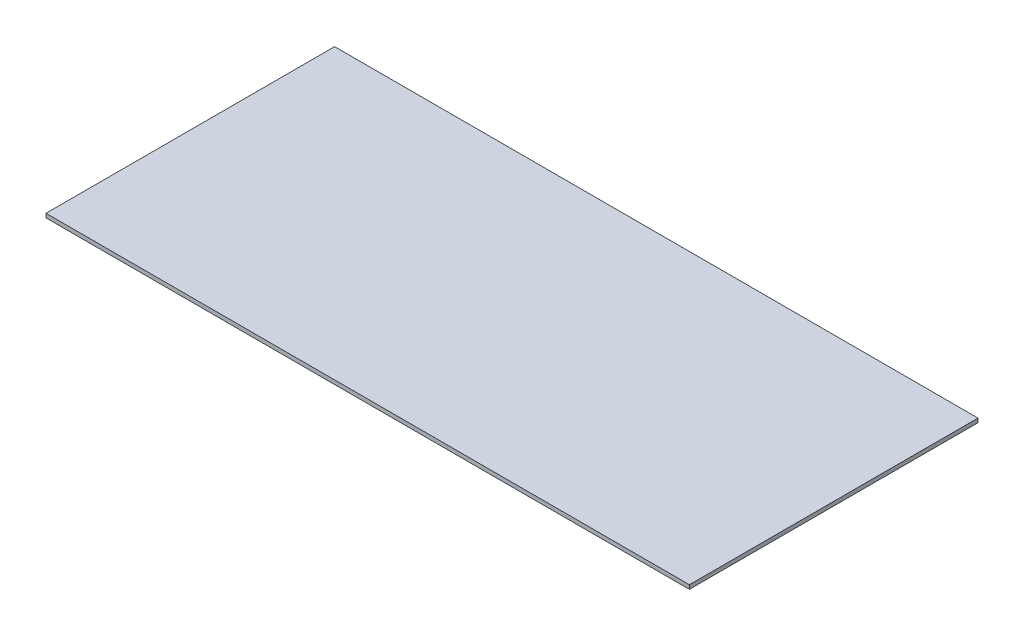
SolidWorks part; units mm, degrees
material "Maple"
ref_plane "Front Plane" through (0, 0, 0) normal (0, 0, 1) x (1, 0, 0)
ref_plane "Top Plane" through (0, 0, 0) normal (0, 1, 0) x (1, 0, 0)
ref_plane "Right Plane" through (0, 0, 0) normal (1, 0, 0) x (0, 0, -1)
sketch "Sketch1" plane through (0, 0, 0) normal (0, 1, 0) x (1, 0, 0)
  line L1 (0, 0) -> (2038.35, 0)
  line L2 (0, 0) -> (0, 914.4)
  line L3 (0, 914.4) -> (2038.35, 914.4)
  line L4 (2038.35, 0) -> (2038.35, 914.4)
  dimension "D1" = 914.4
  dimension "D2" = 2038.35
extrude "Boss-Extrude1" add sketch "Sketch1" along normal blind 12.7
